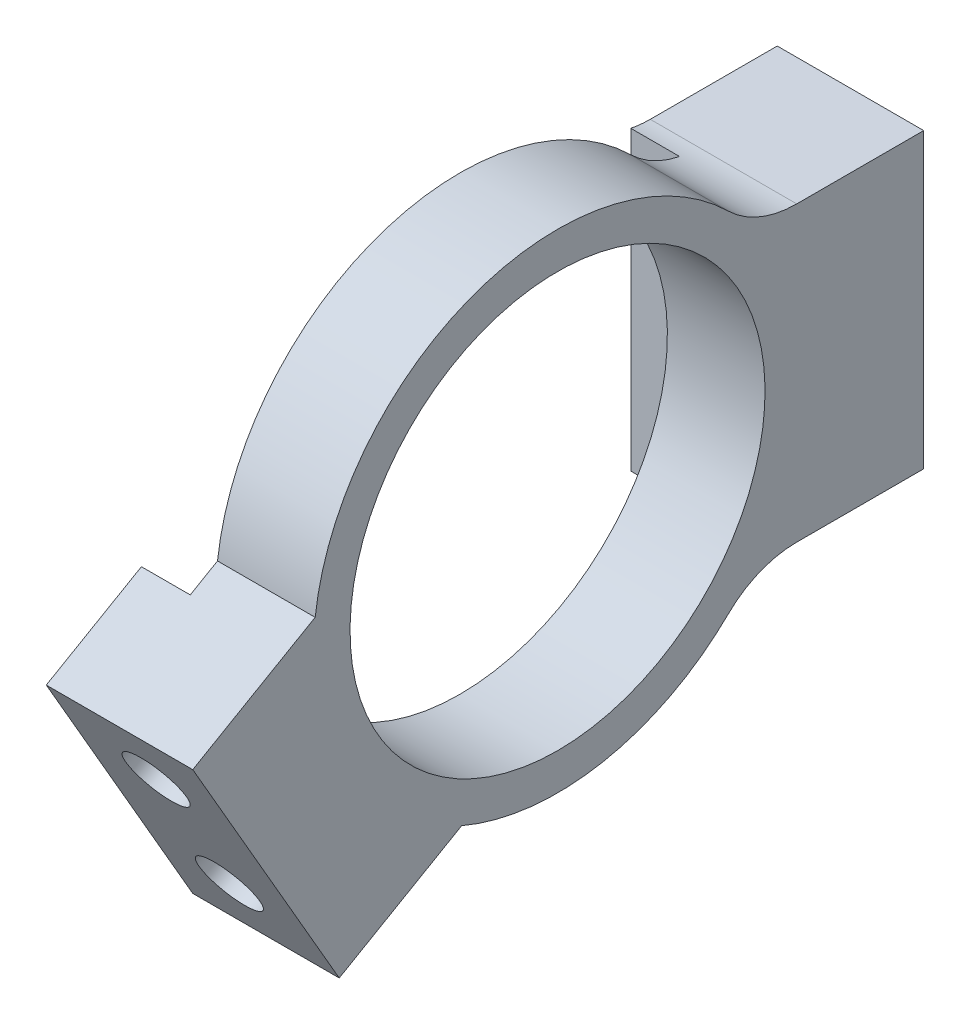
SolidWorks part; units mm, degrees
note: '?' marks a value the reader was unsure of.
ref_plane "Front" through (0, 0, 0) normal (0, 0, 1) x (1, 0, 0)
ref_plane "Top" through (0, 0, 0) normal (0, 1, 0) x (1, 0, 0)
ref_plane "Right" through (0, 0, 0) normal (1, 0, 0) x (0, 0, -1)
sketch "Sketch1" plane through (0, 0, 0) normal (0, 0, 1) x (1, 0, 0)
  line L1 (-4, 6) -> (2, 6)
  line L2 (-4, 6) -> (-4, -6)
  line L3 (-4, -6) -> (2, -6)
  line L4 (2, 6) -> (2, -6)
  dimension "D1" = 6
  dimension "D2" = 6
  dimension "D3" = 4
  dimension "D4" = 2
extrude "Extrude1" add sketch "Sketch1" along normal blind 6
sketch "Sketch2" plane through (0, 0, 0) normal (0, 0, -1) x (-1, 0, 0)
  line L0 (-2, 6) -> (4, 6) construction
  line L1 (4, -6) -> (-2, -6) construction
  line L2 (4, 6) -> (4, -6) construction
  circle A0 centre (1, 3) radius 1.25
  circle A1 centre (1, -3) radius 1.25
  dimension "D2" = 2.5
  dimension "D3" = 2.5
  dimension "D1" = 3
  dimension "D4" = 3
  dimension "D5" = 3
sketch "Sketch3" plane through (0, 0, 6) normal (0, 0, 1) x (1, 0, 0)
  line L1 (-2, 4.3) -> (2, 4.3)
  line L2 (-2, 4.3) -> (-2, -4.3)
  line L3 (-2, -4.3) -> (2, -4.3)
  line L4 (2, 4.3) -> (2, -4.3)
  dimension "D1" = 2
  dimension "D2" = 2
  dimension "D3" = 4.3
  dimension "D4" = 4.3
extrude "Extrude2" add sketch "Sketch3" along normal blind 1
extrude "Extrude3" cut sketch "Sketch2" against normal blind 5.5
cosmetic thread "Hole Thread1" parameters "D1"=4.5, "D2"=3
cosmetic thread "Hole Thread2" parameters "D1"=4.5, "D2"=3
cosmetic thread "Hole Thread3" parameters "D1"=4.5, "D2"=3
cosmetic thread "Hole Thread4" parameters "D1"=4.5, "D2"=3
cosmetic thread "Hole Thread7" parameters "D1"=4.5, "D2"=3
cosmetic thread "Hole Thread8" parameters "D1"=4.5, "D2"=3
cosmetic thread "Hole Thread11" parameters "D1"=4.5, "D2"=3
cosmetic thread "Hole Thread12" parameters "D1"=4.5, "D2"=3
cosmetic thread "Hole Thread13" parameters "D1"=4.5, "D2"=3
cosmetic thread "Hole Thread14" parameters "D1"=4.5, "D2"=3
cosmetic thread "Hole Thread15" parameters "D1"=4, "D2"=3
cosmetic thread "Hole Thread16" parameters "D1"=4, "D2"=3
cosmetic thread "Hole Thread17" parameters "D1"=3.5, "D2"=3
cosmetic thread "Hole Thread18" parameters "D1"=3.5, "D2"=3
cosmetic thread "Hole Thread19" parameters "D1"=3, "D2"=3
cosmetic thread "Hole Thread20" parameters "D1"=3, "D2"=3
cosmetic thread "Hole Thread21" parameters "D1"=3, "D2"=3
cosmetic thread "Hole Thread22" parameters "D1"=3, "D2"=3
cosmetic thread "Hole Thread23" parameters "D1"=2, "D2"=3
cosmetic thread "Hole Thread24" parameters "D1"=2, "D2"=3
cosmetic thread "Hole Thread25" parameters "D1"=2, "D2"=3
cosmetic thread "Hole Thread26" parameters "D1"=2, "D2"=3
sketch "Sketch4" plane through (2, 0, 0) normal (1, 0, 0) x (0, 0, -1)
  line L0 (-7, 6) -> (-6, 6)
  line L1 (-7, -4.3) -> (-7, 4.3) construction
  line L2 (-6, 6) -> (-6, -6)
  line L3 (-6, -6) -> (-7, -6)
  arc A0 (-7, 6) -> (-7, -6) centre (-15, 0) ccw
  dimension "D2" = 10
  dimension "D1" = 8
extrude "Extrude4" add sketch "Sketch4" against normal blind 4
sketch "Sketch6" plane through (-2, 0, 0) normal (-1, 0, 0) x (0, 0, 1)
  circle A0 centre (15, 0) radius 8.5
  dimension "D1" = 17
extrude "Extrude5" cut sketch "Sketch6" against normal up to surface (4 mm away) up to face at (2, 0, 8)
ref_axis "Axis1" through (2, 0, 15) along (-1, 0, 0)?
fillet "Fillet1" radius 4 2 edges at (0, 6, 7) (0, -6, 7)
sketch "Sketch12" plane through (-2, 0, 0) normal (-1, 0, 0) x (0, 0, 1)
  line L0 (23.9425, -12.0912) -> (18.9282, -9.1962)
  line L1 (29.9425, -1.6988) -> (24.9282, 1.1962)
  line L2 (29.9425, -1.6988) -> (23.9425, -12.0912)
  arc A0 (8.0015, -7.1429) -> (8.0015, 7.1429) centre (15, 0) ccw construction
  arc A2 (24.9282, 1.1962) -> (18.9282, -9.1962) centre (15, 0) cw
  arc M7 (8.0015, -7.1429) -> (8.0015, 7.1429) centre (15, 0) ccw
  dimension "D1" = 12
  dimension "D3" = 5.79
  dimension "D4" = 5.79
extrude "Extrude9" add sketch "Sketch12" against normal up to surface (4 mm away) contours L2 L1 L0 M7 up to face at (2, -8.5, 15)
sketch "Sketch13" plane through (-2, 0, 0) normal (-1, 0, 0) x (0, 0, 1)
  line L0 (29.9425, -1.6988) -> (26.0454, 0.5512)
  line L1 (29.9425, -1.6988) -> (24.9282, 1.1962) construction
  line L2 (26.0454, 0.5512) -> (20.0454, -9.8412)
  line L3 (23.9425, -12.0912) -> (18.9282, -9.1962) construction
  line L4 (20.0454, -9.8412) -> (23.9425, -12.0912)
  line L5 (23.9425, -12.0912) -> (29.9425, -1.6988)
  dimension "D1" = 4.5
extrude "Extrude10" add sketch "Sketch13" along normal up to surface (2 mm away) up to face at (-4, 0, 3.7347)
sketch "Sketch14" plane through (0, -13.3902, 23.1925) normal (0, -0.5, 0.866) x (1, 0, 0)
  line L0 (-4, 13.5) -> (-4, 1.5) construction
  line L2 (2, 13.5) -> (-4, 13.5) construction
  line L3 (2, 1.5) -> (-4, 1.5) construction
  circle A0 centre (-1, 4.5) radius 1.25
  circle A1 centre (-1, 10.5) radius 1.25
  dimension "D1" = 2.5
  dimension "D2" = 2.5
  dimension "D3" = 3
  dimension "D4" = 3
  dimension "D5" = 3
  dimension "D6" = 3
extrude "Extrude11" cut sketch "Sketch14" against normal blind 4
cosmetic thread "Hole Thread5" parameters "D1"=4, "D2"=3
cosmetic thread "Hole Thread6" parameters "D1"=4, "D2"=3
